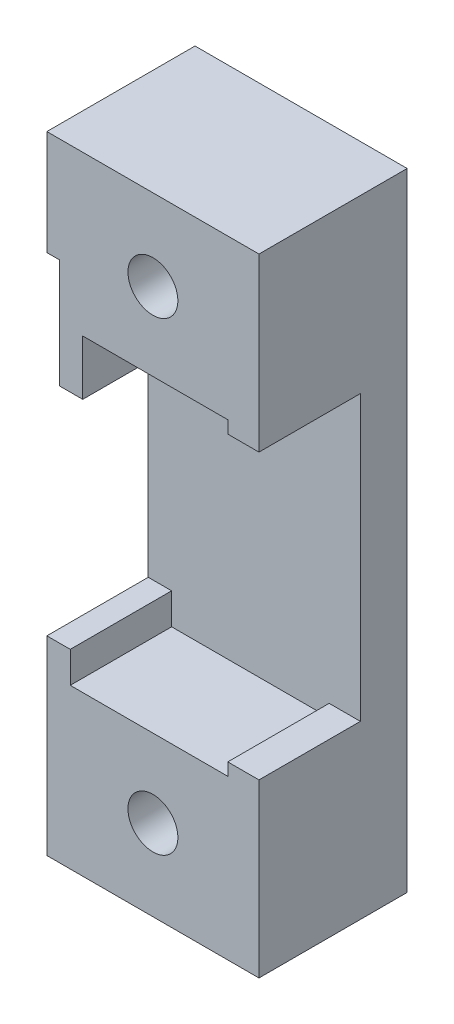
SolidWorks part; units mm, degrees
ref_plane "Front Plane" through (0, 0, 0) normal (1, 0, 0) x (0, 1, 0)
ref_plane "Top Plane" through (0, 0, 0) normal (0, 0, 1) x (0, 1, 0)
ref_plane "Right Plane" through (0, 0, 0) normal (0, 1, 0) x (-1, 0, 0)
sketch "Sketch1" plane through (0, 0, 0) normal (0, 0, 1) x (0, 1, 0)
  line L0 (-9.9, 0) -> (-9.1, 0)
  line L1 (-9.9, 0) -> (-9.9, 10.1)
  line L2 (9.9, 0) -> (9.9, 9.3)
  line L3 (-9.1, 0) -> (-9.1, -2)
  line L4 (9.9, 0) -> (9.1, 0)
  line L5 (9.1, 0) -> (9.1, -2)
  line L6 (9.1, -2) -> (20.1, -2)
  line L7 (20.1, -2) -> (20.1, 11.6)
  line L9 (6.3789, 10.8) -> (6.3789, 9.3)
  line L10 (6.3789, 9.3) -> (9.9, 9.3)
  line L11 (-9.1, -2) -> (-20.1, -2)
  line L12 (-20.1, -2) -> (-20.1, 11.6)
  line L13 (-20.1, 11.6) -> (-7.9, 11.6)
  line L14 (-7.9, 11.6) -> (-7.9, 10.1)
  line L15 (-7.9, 10.1) -> (-9.9, 10.1)
  line L16 (9.1, 0) -> (-9.1, 0) construction
  line L17 (-9.1, -2) -> (9.1, -2)
  line L18 (6.3789, 10.8) -> (13.3789, 10.8)
  line L19 (13.3789, 10.8) -> (13.3789, 11.6)
  line L20 (13.3789, 11.6) -> (20.1, 11.6)
  line L21 (-20.1, 4.8) -> (-14.9, 4.8) construction
  line L22 (0, 0) -> (0, 4.8) construction
  line L23 (-14.9, 4.8) -> (14.9, 4.8) construction
  line L24 (14.9, 4.8) -> (20.1, 4.8) construction
  line L25 (-7.9, 11.6) -> (13.3789, 11.6)
  circle A0 centre (14.9, 4.8) radius 1.6
  circle A1 centre (14.9, 4.8) radius 2.85
  circle A2 centre (-14.9, 4.8) radius 1.6
  circle A3 centre (-14.9, 4.8) radius 2.85
  point P4 (0, 0)
  point P21 (0, 0)
  dimension "D14" = 3.2
  dimension "D15" = 5.7
  dimension "D16" = 3.2
  dimension "D17" = 5.7
  dimension "D1" = 19.8
  dimension "D2" = 10.1
  dimension "D3" = 9.3
  dimension "D4" = 1.5
  dimension "D5" = 1.5
  dimension "D6" = 0.8
  dimension "D7" = 0.8
  dimension "D8" = 2
  dimension "D9" = 2
  dimension "D10" = 7
  dimension "D11" = 40.2
  dimension "D12" = 5.2
  dimension "D13" = 5.2
  dimension "D18" = 2
extrude "Boss-Extrude1" add sketch "Sketch1" along normal blind 6.5 contours L15 L14 L13 L12 L11 L3 L0 L1 A3 | L20 L19 L18 L9 L10 L2 L4 L5 L6 L7 A1 | A3 A2 | A1 A0 region at (0.1827, -9.5, 0) region at (1, 9.2932, 0) region at (-4.8, 12.1306, 0) region at (-4.8, -17.6694, 0)
extrude "Boss-Extrude2" add sketch "Sketch1<3>" against normal blind 3 contours A1 A0 | L20 L19 L18 L9 L10 L2 L4 L5 L6 L7 A1 | L25 L14 L15 L1 L0 L3 L17 L5 L4 L2 L10 L9 L18 L19 | A3 A2 | L15 L14 L13 L12 L11 L3 L0 L1 A3 region at (-4.7635, 0.0618, 0) region at (0.1827, -9.5, 0) region at (1, 9.2932, 0) region at (-4.8, 12.1306, 0) region at (-4.8, -17.6694, 0)
sketch "Sketch1<3>" plane through (0, 0, 0) normal (0, 0, 1) x (0, 1, 0) same geometry as "Sketch1"
extrude "Cut-Extrude1" cut sketch "Sketch1<4>" along normal blind 3.5 and the other way through all from surface contours A1 | A3 starting at face at (-4.8, 0, -3)
sketch "Sketch1<4>" plane through (0, 0, 0) normal (0, 0, 1) x (0, 1, 0) same geometry as "Sketch1"
